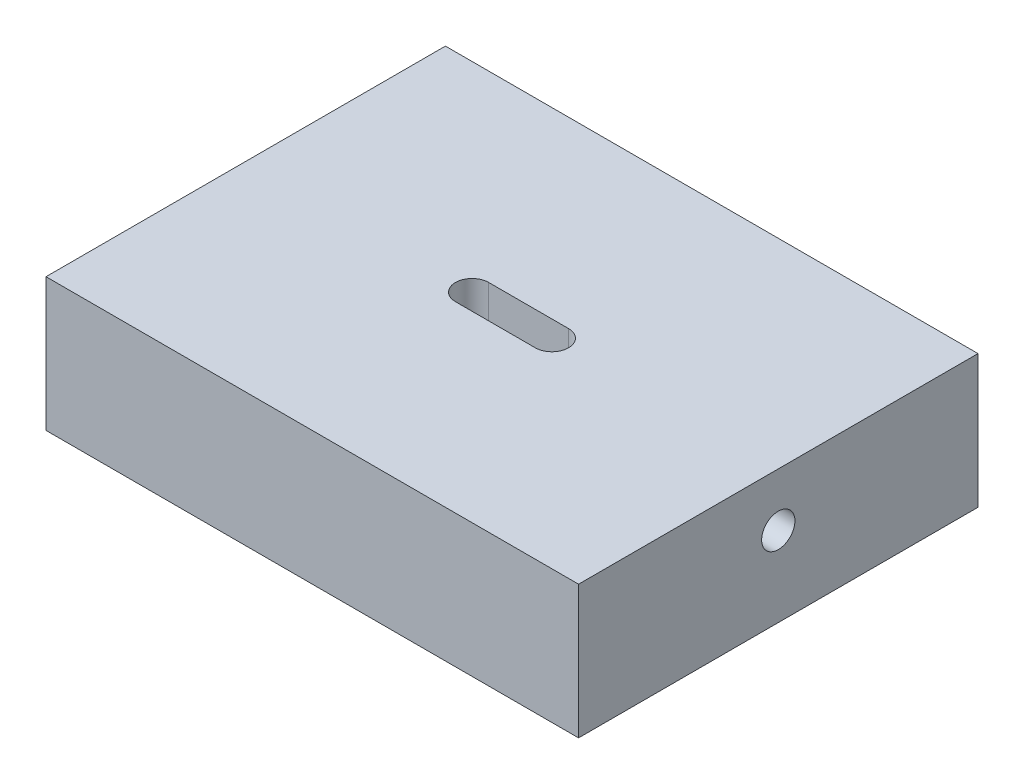
SolidWorks part; units mm, degrees
material "Acrylic (Medium-high impact)"
ref_plane "Front Plane" through (0, 0, 0) normal (0, 0, 1) x (1, 0, 0)
ref_plane "Top Plane" through (0, 0, 0) normal (0, 1, 0) x (1, 0, 0)
ref_plane "Right Plane" through (0, 0, 0) normal (1, 0, 0) x (0, 0, -1)
sketch "Sketch1" plane through (0, 0, 0) normal (0, 1, 0) x (1, 0, 0)
  line L1 (-25.4, 19.05) -> (25.4, 19.05)
  line L2 (-25.4, 19.05) -> (-25.4, -19.05)
  line L3 (-25.4, -19.05) -> (25.4, -19.05)
  line L4 (25.4, 19.05) -> (25.4, -19.05)
  line L5 (-25.4, 19.05) -> (25.4, -19.05) construction
  line L6 (-25.4, -19.05) -> (25.4, 19.05) construction
  point P0 (0, 0)
  dimension "D1" = 50.8
  dimension "D2" = 38.1
extrude "Boss-Extrude1" add sketch "Sketch1" along normal blind 12.7
sketch "Sketch2" plane through (25.4, 0, 0) normal (1, 0, 0) x (0, 0, -1)
  line L0 (-19.05, 0) -> (19.05, 0) construction
  circle A0 centre (0, 7.62) radius 1.5875
  point P4 (0, 0)
  point P6 (0, 0)
  dimension "D2" = 3.175
  dimension "D1" = 7.62
extrude "Cut-Extrude1" cut sketch "Sketch2" against normal blind 31.75
sketch "Sketch3" plane through (0, 12.7, 0) normal (0, 1, 0) x (1, 0, 0)
  line L0 (-3.81, 0) -> (3.81, 0) construction
  line L1 (-3.81, 1.5875) -> (3.81, 1.5875)
  line L2 (-3.81, -1.5875) -> (3.81, -1.5875)
  arc A0 (-3.81, 1.5875) -> (-3.81, -1.5875) centre (-3.81, 0) ccw
  arc A1 (3.81, -1.5875) -> (3.81, 1.5875) centre (3.81, 0) ccw
  point P3 (0, 0)
  point P8 (0, 0)
  dimension "D1" = 3.175
  dimension "D2" = 7.62
extrude "Cut-Extrude2" cut sketch "Sketch3" against normal blind 5.08
sketch "Sketch4" plane through (0, 0, 0) normal (0, -1, 0) x (1, 0, 0)
  circle A0 centre (0, 0) radius 1.5875
  circle A1 centre (19.05, 0) radius 1.5875
  dimension "D1" = 3.175
  dimension "D2" = 19.05
extrude "Cut-Extrude3" cut sketch "Sketch4" against normal blind 7.62
chamfer "Chamfer1" distance 0.635 angle 45 2 edges at (19.05, 0, -1.5875) (0, 0, -1.5875)
thread "Thread1" pitch 0.7937 method cut profile "Thread Profile1" start angle 0, offset 1.016, length 7.62, pitch 0.7937, diameter 3.175
ref_plane "Plane1" through (1.5875, -0.381, 0) normal (0, 0, 1) x (1, 0, 0)
sketch "Thread Profile1" plane through (1.5875, -0.381, 0) normal (0, 0, 1) x (1, 0, 0)
  line L0 (0, 0) -> (0, 0.7937) construction
  line L1 (0, 0) -> (0.4296, 0.248)
  line L2 (0.4296, 0.248) -> (0.4296, 0.3473)
  line L3 (0.4296, 0.3473) -> (0, 0.5953)
  line L4 (0.4296, 0.2977) -> (0, 0.2977) construction
  line L11 (0, 0) -> (0, 0.5953)
  point P2 (0, 0)
  dimension "Pitch" = 0.7937
  dimension "Profile_Angle" = 60
  dimension "Profile_Land" = 0.0992
  dimension "Profile_Height" = 0.4296
thread "Thread2" pitch 0.7937 method cut profile "Thread Profile2" start angle 0, offset 1.016, length 7.62, pitch 0.7937, diameter 3.175
ref_plane "Plane2" through (20.6375, -0.381, 0) normal (0, 0, 1) x (1, 0, 0)
sketch "Thread Profile2" plane through (20.6375, -0.381, 0) normal (0, 0, 1) x (1, 0, 0)
  line L0 (0, 0) -> (0, 0.7937) construction
  line L1 (0, 0) -> (0.4296, 0.248)
  line L2 (0.4296, 0.248) -> (0.4296, 0.3473)
  line L3 (0.4296, 0.3473) -> (0, 0.5953)
  line L4 (0.4296, 0.2977) -> (0, 0.2977) construction
  line L11 (0, 0) -> (0, 0.5953)
  point P2 (0, 0)
  dimension "Pitch" = 0.7937
  dimension "Profile_Angle" = 60
  dimension "Profile_Land" = 0.0992
  dimension "Profile_Height" = 0.4296
